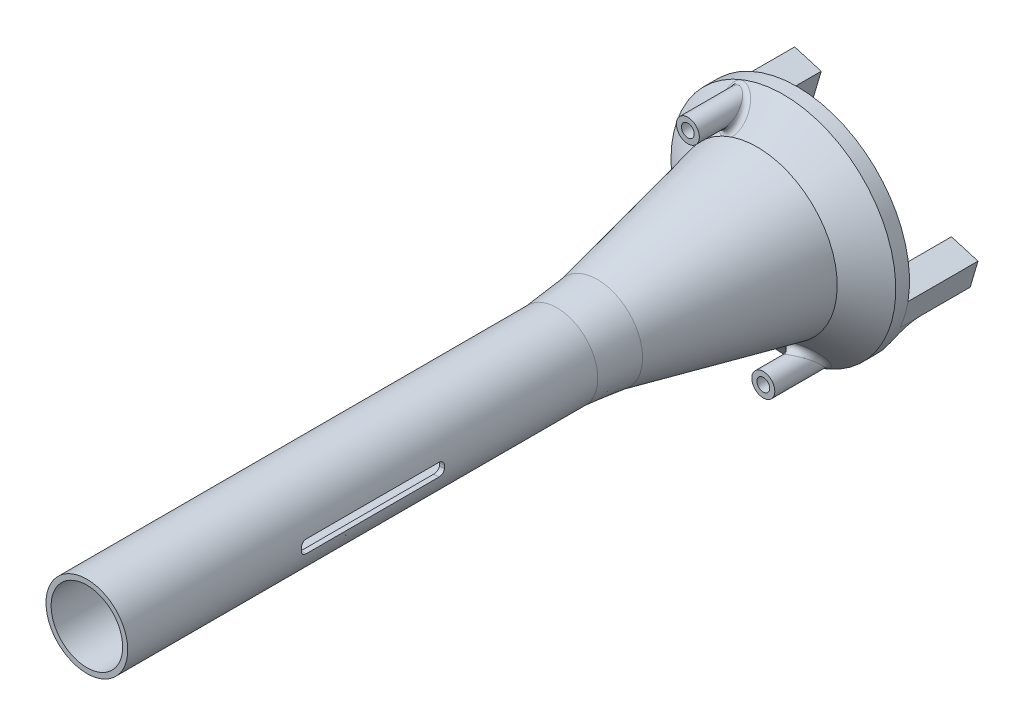
SolidWorks part; units mm, degrees
material "AISI 1020"
ref_plane "Front Plane" through (0, 0, 0) normal (1, 0, 0) x (0, 1, 0)
ref_plane "Top Plane" through (0, 0, 0) normal (0, 0, 1) x (0, 1, 0)
ref_plane "Right Plane" through (0, 0, 0) normal (0, 1, 0) x (-1, 0, 0)
sketch "Sketch1" plane through (0, 0, 0) normal (1, 0, 0) x (0, 1, 0)
  line L0 (0, 0) -> (50.8, 0) construction
  line L1 (50.8, 0) -> (50.8, 4.7625)
  line L2 (50.8, 0) -> (69.85, 0)
  line L3 (69.85, 0) -> (69.85, 4.7625)
  line L4 (0, 0) -> (0, 149.225) construction
  line L5 (0, 149.225) -> (22.225, 149.225) construction
  line L6 (22.225, 149.225) -> (22.225, 136.1838)
  line L7 (22.225, 149.225) -> (25.4, 149.225)
  line L8 (25.4, 149.225) -> (25.4, 136.525)
  line L9 (22.225, 136.1838) -> (50.8, 4.7625)
  line L11 (69.85, 4.7625) -> (54.0492, 4.7625)
  line L12 (54.0492, 4.7625) -> (25.4, 136.525)
  dimension "D1" = 19.05
  dimension "D2" = 69.85
  dimension "D3" = 4.7625
  dimension "D4" = 22.225
  dimension "D5" = 149.225
  dimension "D6" = 3.175
  dimension "D7" = 3.175
  dimension "D8" = 12.7
revolve "Revolve1" add sketch "Sketch1" angle 360 about L4
chamfer "Chamfer1" distance 2.032 angle 45 1 edges at (-50.8, 0, 0)
sketch "Sketch2" plane through (0, 0, 0) normal (0, 0, -1) x (1, 0, 0)
  line L0 (-52.4269, -6.5302) -> (-68.9131, -11.4021)
  line L1 (-44.45, -152.4) -> (44.45, -152.4) construction
  line L2 (-44.45, -152.4) -> (-44.45, 152.4) construction
  line L3 (-44.45, 152.4) -> (44.45, 152.4) construction
  line L4 (44.45, -152.4) -> (44.45, 152.4) construction
  line L5 (-44.45, -152.4) -> (44.45, 152.4) construction
  line L6 (-44.45, 152.4) -> (44.45, -152.4) construction
  line L7 (-68.9131, -11.4021) -> (-64.0411, -27.8884)
  line L8 (-64.0411, -27.8884) -> (-47.5549, -23.0164)
  line L9 (-47.5549, -23.0164) -> (-52.4269, -6.5302)
  circle A0 centre (0, 0) radius 52.832 construction
  circle A1 centre (0, 0) radius 69.85 construction
  circle A3 centre (0, 0) radius 69.85
  point P0 (0, 0)
  point P7 (0, 0)
  point P13 (-44.45, -28.5555)
  circle M2 centre (0, 0) radius 52.832
  dimension "D1" = 88.9
  dimension "D2" = 304.8
  dimension "D3" = 6.35
extrude "Boss-Extrude1" add sketch "Sketch2" along normal blind 43.4975 contours L7 L8 L0 M2
pattern_circular "CirPattern1" count 2 over 360 about axis through (0, 0, 0) along (0, 0, 1) of "Boss-Extrude1"
sketch "Sketch3" plane through (0, 0, 0) normal (0, 0, -1) x (1, 0, 0)
  line L0 (44.45, -152.4) -> (44.45, 152.4) construction
  line L1 (-44.45, -152.4) -> (-44.45, 152.4) construction
  line L2 (44.45, -152.4) -> (44.45, 152.4) construction
  line L3 (-44.45, -152.4) -> (-44.45, 152.4) construction
  line L4 (-20.1881, -48.8227) -> (-26.6911, -64.5493) construction
  line L5 (-20.1881, -48.8227) -> (0, 0) construction
  circle A1 centre (0, 0) radius 69.85 construction
  arc A2 (-52.4269, -6.5302) -> (-46.7696, 24.5728) centre (0, 0) cw construction
  arc A3 (47.5549, 23.0164) -> (-52.4269, -6.5302) centre (0, 0) ccw construction
  arc A5 (-47.5549, -23.0164) -> (52.4269, 6.5302) centre (0, 0) ccw construction
  arc A6 (-20.1881, -48.8227) -> (-44.45, -28.5555) centre (0, 0) cw construction
  point P11 (-23.4396, -56.686)
  point P28 (-44.45, 28.5555)
  dimension "D1" = 5
hole_wizard "5/16 (0.3125) Diameter Hole1" positions "Sketch3" profile "Sketch4" hole size "5/16" standard "ANSI Inch"
sketch "Sketch4" plane through (-23.4396, 56.686, 0) normal (1, 0, 0) x (0, 1, 0)
  line L0 (0, 0) -> (0, 149.225)
  line L1 (0, 149.225) -> (3.9687, 149.225)
  line L2 (3.9687, 149.225) -> (3.9687, 0)
  line L5 (3.9687, 0) -> (0, 0)
  line L11 (0, -6.35) -> (0, 107.95) construction
  dimension "Thru Hole Dia." = 7.9375
  dimension "Thru Hole Depth" = 149.225
sketch "Sketch5" plane through (0, 0, 4.7625) normal (0, 0, 1) x (1, 0, 0)
  circle A0 centre (-23.4396, 56.686) radius 3.9687 construction
  circle A1 centre (0, 0) radius 69.85
  circle A2 centre (0, 0) radius 69.85
  circle A3 centre (-23.4396, 56.686) radius 3.9687
  circle A4 centre (-23.4396, 56.686) radius 7.1437
  dimension "D1" = 0
  dimension "D2" = 3.175
extrude "Boss-Extrude2" add sketch "Sketch5" along normal blind 39.6875
fillet "Chamfer3" radius 25.4 1 edges at (-54.0492, 0, 4.7625)
pattern_circular "CirPattern2" count 2 over 360 about axis through (0, 0, 0) along (0, 0, 1) of "Boss-Extrude2", "5/16 (0.3125) Diameter Hole1"
sketch "Sketch6" plane through (0, 0, -43.4975) normal (0, 0, -1) x (1, 0, 0)
  line L0 (-68.9131, -11.4021) -> (-49.1596, 49.6222) construction
  line L1 (-49.1596, 49.6222) -> (-47.5549, 23.0164) construction
  line L2 (-47.5549, 23.0164) -> (-47.5549, -23.0164) construction
  line L3 (-47.5549, -23.0164) -> (-68.9131, -11.4021) construction
  line L5 (-44.45, -152.4) -> (-44.45, 152.4) construction
  line L6 (-44.45, -152.4) -> (-44.45, 152.4) construction
  line L7 (-68.9131, -11.4021) -> (-64.0411, -27.8884)
  line L8 (-64.0411, -27.8884) -> (-47.5549, -23.0164)
  line L10 (-47.5549, 23.0164) -> (-49.1596, 49.6222)
  line L11 (-52.4269, -6.5302) -> (-47.5549, -23.0164)
  arc A0 (47.5549, 23.0164) -> (-52.4269, -6.5302) centre (0, 0) ccw construction
  circle A1 centre (0, 0) radius 69.85 construction
  arc A2 (-49.1596, 49.6222) -> (-68.9131, -11.4021) centre (0, 0) ccw
  arc A3 (-47.5549, 23.0164) -> (-52.4269, -6.5302) centre (0, 0) ccw
  point P6 (-44.45, 53.8815)
  point P15 (-44.45, 28.5555)
  dimension "D1" = 6.35
  dimension "D2" = 6.35
extrude "Boss-Extrude3" add sketch "Sketch6" along normal blind 19.05
chamfer "Chamfer2" distance 6.35 distance2 39.37 2 edges at (-48.3572, -36.3193, -43.4975) (-60.67, 8.9662, -43.4975)
sketch "Sketch7" plane through (0, 0, 149.225) normal (0, 0, 1) x (1, 0, 0)
  circle A0 centre (0, 0) radius 22.225 construction
  circle A1 centre (0, 0) radius 25.4
  circle A2 centre (0, 0) radius 25.4
  circle A3 centre (0, 0) radius 22.225
  dimension "D1" = 0
extrude "Boss-Extrude4" add sketch "Sketch7" along normal blind 292.1
sketch "Sketch8" plane through (0, 0, 0) normal (1, 0, 0) x (0, 1, 0)
  line L0 (25.4, 441.325) -> (-25.4, 441.325) construction
  line L5 (25.4, 441.325) -> (-25.4, 441.325) construction
  line L6 (25.4, 136.525) -> (25.4, 441.325) construction
  line L7 (-3.9687, 244.475) -> (3.9688, 244.475)
  line L8 (-3.9687, 244.475) -> (-3.9687, 333.375)
  line L9 (-3.9687, 333.375) -> (3.9688, 333.375)
  line L10 (3.9688, 244.475) -> (3.9688, 333.375)
  line L11 (-3.9687, 244.475) -> (3.9688, 333.375) construction
  line L12 (-3.9687, 333.375) -> (3.9688, 244.475) construction
  line L13 (25.4, 136.525) -> (25.4, 441.325) construction
  point P0 (0, 288.925)
  point P7 (0, 441.325)
  point P10 (25.4, 288.925)
  dimension "D1" = 7.9375
  dimension "D2" = 88.9
extrude "Cut-Extrude1" cut sketch "Sketch8" against normal through all both and the other way through all contours L7 L10 L9 L8
fillet "Fillet3" radius 3.175 8 edges at (23.4779, 3.9688, 244.475) (-23.4779, 3.9688, 244.475) (23.4779, -3.9687, 244.475) (-23.4779, -3.9687, 244.475) (23.4779, 3.9688, 333.375) (-23.4779, 3.9688, 333.375) (23.4779, -3.9687, 333.375) (-23.4779, -3.9687, 333.375)
fillet "Fillet6" radius 12.7 2 edges at (-55.798, 25.4524, 0) (55.798, -25.4524, 0)
fillet "Fillet9" radius 3.175 2 edges at (27.0276, -50.5087, 18.6524) (-16.6694, 54.4063, 18.9609)
chamfer "Chamfer4" distance 12.7 1 edges at (-25.4, 0, 136.525)
fillet "Fillet11" radius 2.54 1 edges at (-49.1596, -49.6222, -53.0225)
